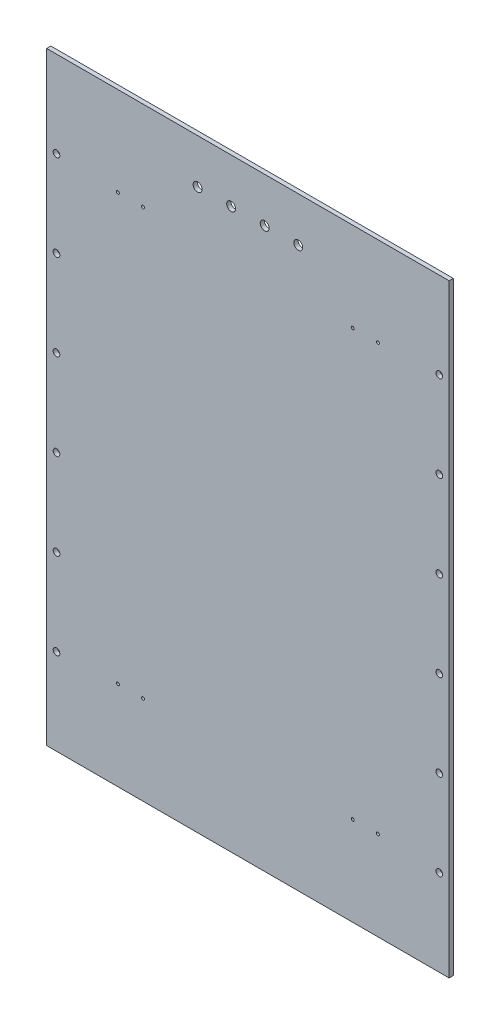
SolidWorks part; units mm, degrees
material "Plain Carbon Steel"
ref_plane "Front Plane" through (0, 0, 0) normal (0, 0, 1) x (1, 0, 0)
ref_plane "Top Plane" through (0, 0, 0) normal (0, 1, 0) x (1, 0, 0)
ref_plane "Right Plane" through (0, 0, 0) normal (1, 0, 0) x (0, 0, -1)
sketch "Sketch1" plane through (0, 0, 0) normal (0, 0, 1) x (1, 0, 0)
  line L1 (-304.8, -457.2) -> (304.8, -457.2)
  line L2 (-304.8, -457.2) -> (-304.8, 457.2)
  line L3 (-304.8, 457.2) -> (304.8, 457.2)
  line L4 (304.8, -457.2) -> (304.8, 457.2)
  line L5 (-304.8, -457.2) -> (304.8, 457.2) construction
  line L6 (-304.8, 457.2) -> (304.8, -457.2) construction
  point P0 (0, 0)
  dimension "D1" = 914.4
  dimension "D2" = 609.6
extrude "Boss-Extrude1" add sketch "Sketch1" along normal mid plane 6.35
sketch "Sketch2" plane through (0, 0, 3.175) normal (0, 0, 1) x (1, 0, 0)
  line L0 (-304.8, -457.2) -> (304.8, -457.2) construction
  line L1 (-304.8, 457.2) -> (-304.8, -457.2) construction
  line L2 (0, 457.2) -> (0, -457.2) construction
  line L3 (304.8, 457.2) -> (-304.8, 457.2) construction
  line L4 (304.8, 0) -> (-304.8, 0) construction
  line L5 (304.8, -457.2) -> (304.8, 457.2) construction
  point P0 (-196.85, -322.2625)
  point P1 (-158.75, -322.2625)
  point P14 (196.85, -322.2625)
  point P15 (158.75, -322.2625)
  point P16 (158.75, 322.2625)
  point P17 (196.85, 322.2625)
  point P18 (-158.75, 322.2625)
  point P19 (-196.85, 322.2625)
  dimension "D1" = 134.9375
  dimension "D2" = 107.95
  dimension "D3" = 38.1
hole_wizard "#8 Clearance Hole1" positions "Sketch2" profile "Sketch3" hole size "#8" standard "ANSI Inch" end condition up to next
sketch "Sketch3" plane through (-196.85, -322.2625, 3.175) normal (1, 0, 0) x (0, -1, 0)
  line L0 (0, 0) -> (0, 6.35)
  line L1 (0, 6.35) -> (2.2479, 6.35)
  line L2 (2.2479, 6.35) -> (2.2479, 0)
  line L5 (2.2479, 0) -> (0, 0)
  line L11 (0, -6.35) -> (0, 107.95) construction
  dimension "Thru Hole Dia." = 4.4958
  dimension "Thru Hole Depth" = 6.35
sketch "Sketch4" plane through (0, 0, 3.175) normal (0, 0, 1) x (1, 0, 0)
  circle A0 centre (76.2, 389.7735) radius 6.7462
  circle A1 centre (76.2, 389.7735) radius 6.7462 construction
  circle A2 centre (-25.4, 389.7735) radius 6.7462 construction
  circle A3 centre (25.4, 389.7735) radius 6.7462 construction
  circle A4 centre (-76.2, 389.7735) radius 6.7462 construction
  circle A5 centre (-25.4, 389.7735) radius 6.7462
  circle A6 centre (25.4, 389.7735) radius 6.7462
  circle A7 centre (-76.2, 389.7735) radius 6.7462
  point P5 (76.2, 389.7735)
extrude "Cut-Extrude1" cut sketch "Sketch4" against normal through all both and the other way through all
sketch "Sketch8" plane through (0, 0, 3.175) normal (0, 0, 1) x (1, 0, 0)
  line L0 (-304.8, 457.2) -> (-304.8, -457.2) construction
  line L1 (-304.8, -457.2) -> (304.8, -457.2) construction
  line L2 (0, 457.2) -> (0, -457.2) construction
  line L3 (304.8, 457.2) -> (-304.8, 457.2) construction
  circle A0 centre (158.75, -322.2625) radius 2.2479 construction
  point P0 (-289.8775, -326.5714)
  point P7 (-289.8775, -195.9429)
  point P8 (-289.8775, -65.3143)
  point P9 (-289.8775, 65.3143)
  point P10 (-289.8775, 195.9429)
  point P11 (-289.8775, 326.5714)
  point P17 (289.8775, 326.5714)
  point P18 (289.8775, 195.9429)
  point P19 (289.8775, 65.3143)
  point P20 (289.8775, -65.3143)
  point P21 (289.8775, -195.9429)
  point P22 (289.8775, -326.5714)
  dimension "D1" = 14.9225
  dimension "D2" = 130.6286
  dimension "D4" = 126.3196
  dimension "D3" = 6
hole_wizard "3/8 Clearance Hole1" positions "Sketch8" profile "Sketch9" hole size "3/8" standard "ANSI Inch" end condition up to next
sketch "Sketch9" plane through (-289.8775, -326.5714, 3.175) normal (1, 0, 0) x (0, -1, 0)
  line L0 (0, 0) -> (0, 6.35)
  line L1 (0, 6.35) -> (5.0419, 6.35)
  line L2 (5.0419, 6.35) -> (5.0419, 0)
  line L5 (5.0419, 0) -> (0, 0)
  line L11 (0, -6.35) -> (0, 107.95) construction
  dimension "Thru Hole Dia." = 10.0838
  dimension "Thru Hole Depth" = 6.35
